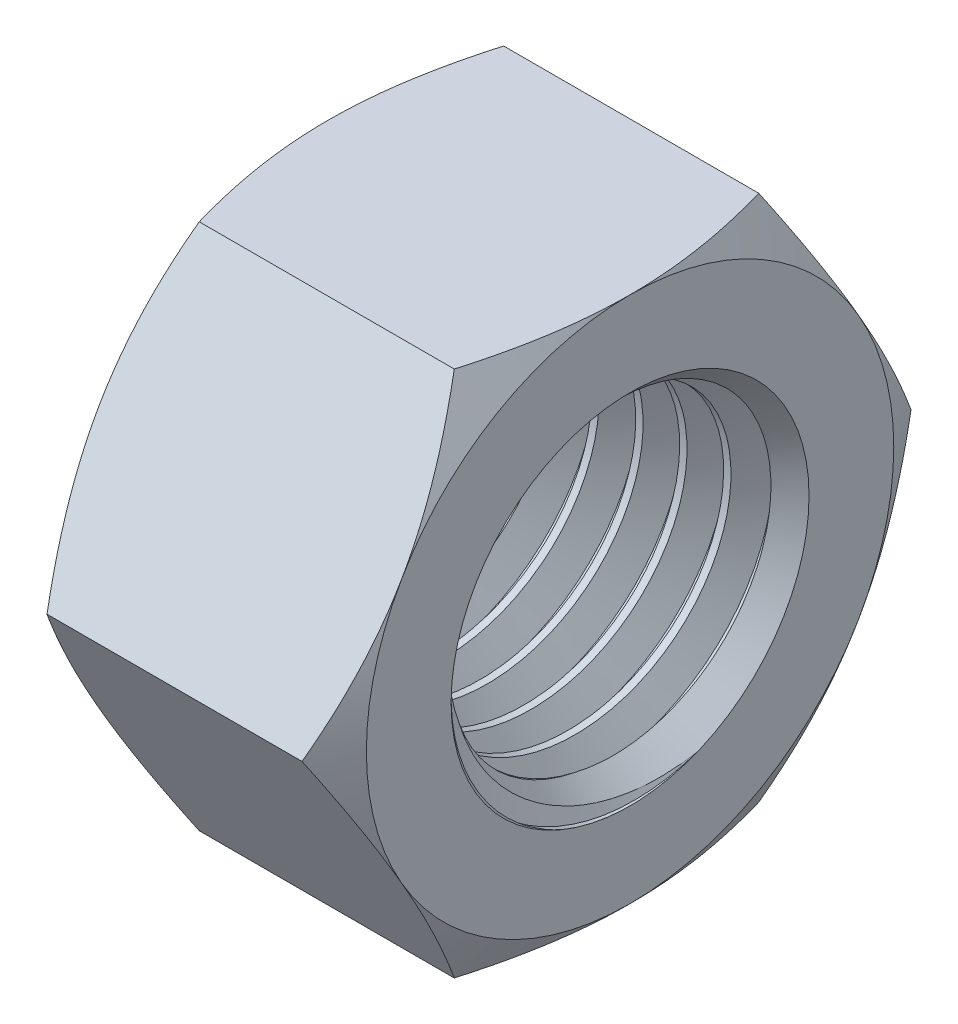
SolidWorks part; units mm, degrees
ref_plane "Front Plane" through (0, 0, 0) normal (0, 0, 1) x (1, 0, 0)
ref_plane "Top Plane" through (0, 0, 0) normal (0, 1, 0) x (1, 0, 0)
ref_plane "Right Plane" through (0, 0, 0) normal (1, 0, 0) x (0, 0, -1)
sketch "Sketch1" plane through (0, 0, 0) normal (1, 0, 0) x (0, 0, -1)
  line L1 (21.997, 0) -> (10.9985, 19.05)
  line L2 (10.9985, 19.05) -> (-10.9985, 19.05)
  line L3 (-10.9985, 19.05) -> (-21.997, 0)
  line L4 (-21.997, 0) -> (-10.9985, -19.05)
  line L5 (-10.9985, -19.05) -> (10.9985, -19.05)
  line L6 (10.9985, -19.05) -> (21.997, 0)
  circle A0 centre (0, 0) radius 19.05 construction
  circle A1 centre (0, 0) radius 10.9817
  dimension "D2" = 21.9634
  dimension "D1" = 38.1
extrude "Boss-Extrude1" add sketch "Sketch1" along normal mid plane 21.8281
sketch "Sketch2" plane through (10.9141, 0, 0) normal (1, 0, 0) x (0, 0, -1)
  line L0 (21.997, 0) -> (10.9985, 19.05) construction
  circle A0 centre (0, 0) radius 19.05
sketch "Sketch3" plane through (0, 0, 0) normal (0, 1, 0) x (1, 0, 0)
  line L0 (10.9141, 19.05) -> (7.2479, 25.4)
  line L1 (10.9141, 21.997) -> (10.9141, 10.9985) construction
  line L2 (7.2479, 25.4) -> (10.9141, 25.4)
  line L3 (10.9141, 25.4) -> (10.9141, 19.05)
  line L6 (-12.4808, 0) -> (21.7087, 0) construction
  line L7 (-12.0055, 0) -> (12.0055, 0) construction
  dimension "D1" = 30
  dimension "D2" = 6.35
revolve "Cut-Revolve1" cut sketch "Sketch3" angle 360 about L6
mirror "Mirror1" about plane through (0, 0, 0) normal (1, 0, 0) of "Cut-Revolve1"
chamfer "Chamfer1" distance 1.9482 angle 45 2 edges at (-10.9141, 0, -10.9817) (10.9141, 0, -10.9817)
ref_plane "Plane1" through (14.0891, 0, 0) normal (1, 0, 0) x (0, 0, -1)
sketch "Sketch4" plane through (14.0891, 0, 0) normal (1, 0, 0) x (0, 0, -1)
  circle A0 centre (0, 0) radius 10.9817 construction
  circle A1 centre (0, 0) radius 10.9817
curve "Helix/Spiral1" pitch 3.175 height 31.75 radius 10.9817 centre (14.0891, 0, 0) axis (-1, 0, 0) start towards (0, 0, -1)
sketch "Sketch5" plane through (0, 0, 0) normal (0, 0, 1) x (1, 0, 0)
  line L0 (14.0891, -13.4075) -> (14.0891, 4.6562) construction
  line L1 (14.0891, -20.955) -> (14.0891, 20.955) construction
  line L2 (7.7438, -10.9812) -> (21.2497, -10.9812) construction
  line L3 (13.8906, -12.9294) -> (14.2876, -12.9294)
  line L4 (14.2876, -12.9294) -> (15.5129, -10.807)
  line L5 (13.8906, -12.9294) -> (12.6652, -10.807)
  line L6 (15.5129, -10.807) -> (12.6652, -10.807)
  spline S0 degree 3 poles (14.0891, -10.9817) (14.0233, -10.9817) (13.8904, -10.4099) (13.6922, -7.9674) (13.4937, -4.3119) (13.2953, 0) (13.0969, 4.3119) (12.8984, 7.9674) (12.7, 10.4099) (12.5016, 11.2676) (12.3031, 10.4099) (12.1047, 7.9674) (11.8401, 3.0934) (11.5755, -3.0934) (11.3109, -7.9674) (11.1125, -10.4099) (10.9141, -11.2676) (10.7156, -10.4099) (10.5172, -7.9674) (10.2526, -3.0934) (9.988, 3.0934) (9.7234, 7.9674) (9.525, 10.4099) (9.3266, 11.2676) (9.1281, 10.4099) (8.9297, 7.9674) (8.6651, 3.0934) (8.4005, -3.0934) (8.1359, -7.9674) (7.9375, -10.4099) (7.7391, -11.2676) (7.5406, -10.4099) (7.3422, -7.9674) (7.0776, -3.0934) (6.813, 3.0934) (6.5484, 7.9674) (6.35, 10.4099) (6.1516, 11.2676) (5.9531, 10.4099) (5.7547, 7.9674) (5.4901, 3.0934) (5.2255, -3.0934) (4.9609, -7.9674) (4.7625, -10.4099) (4.5641, -11.2676) (4.3656, -10.4099) (4.1672, -7.9674) (3.9026, -3.0934) (3.638, 3.0934) (3.3734, 7.9674) (3.175, 10.4099) (2.9766, 11.2676) (2.7781, 10.4099) (2.5797, 7.9674) (2.3151, 3.0934) (2.0505, -3.0934) (1.7859, -7.9674) (1.5875, -10.4099) (1.3891, -11.2676) (1.1906, -10.4099) (0.9922, -7.9674) (0.7276, -3.0934) (0.463, 3.0934) (0.1984, 7.9674) (0, 10.4099) (-0.1984, 11.2676) (-0.3969, 10.4099) (-0.5953, 7.9674) (-0.8599, 3.0934) (-1.1245, -3.0934) (-1.3891, -7.9674) (-1.5875, -10.4099) (-1.7859, -11.2676) (-1.9844, -10.4099) (-2.1828, -7.9674) (-2.4474, -3.0934) (-2.712, 3.0934) (-2.9766, 7.9674) (-3.175, 10.4099) (-3.3734, 11.2676) (-3.5719, 10.4099) (-3.7703, 7.9674) (-4.0349, 3.0934) (-4.2995, -3.0934) (-4.5641, -7.9674) (-4.7625, -10.4099) (-4.9609, -11.2676) (-5.1594, -10.4099) (-5.3578, -7.9674) (-5.6224, -3.0934) (-5.887, 3.0934) (-6.1516, 7.9674) (-6.35, 10.4099) (-6.5484, 11.2676) (-6.7469, 10.4099) (-6.9453, 7.9674) (-7.2099, 3.0934) (-7.4745, -3.0934) (-7.7391, -7.9674) (-7.9375, -10.4099) (-8.1359, -11.2676) (-8.3344, -10.4099) (-8.5328, -7.9674) (-8.7974, -3.0934) (-9.062, 3.0934) (-9.3266, 7.9674) (-9.525, 10.4099) (-9.7234, 11.2676) (-9.9219, 10.4099) (-10.1203, 7.9674) (-10.3849, 3.0934) (-10.6495, -3.0934) (-10.9141, -7.9674) (-11.1125, -10.4099) (-11.3109, -11.2676) (-11.5094, -10.4099) (-11.7078, -7.9674) (-11.9724, -3.0934) (-12.237, 3.0934) (-12.5016, 7.9674) (-12.7, 10.4099) (-12.8984, 11.2676) (-13.0969, 10.4099) (-13.2953, 7.9674) (-13.5599, 3.0934) (-13.8245, -3.0934) (-14.0891, -7.9674) (-14.2875, -10.4099) (-14.4859, -11.2676) (-14.6844, -10.4099) (-14.8828, -7.9674) (-15.1474, -3.0934) (-15.412, 3.0934) (-15.6766, 7.9674) (-15.875, 10.4099) (-16.0734, 11.2676) (-16.2719, 10.4099) (-16.4703, 7.9674) (-16.6687, 4.3119) (-16.8672, 0) (-17.0656, -4.3119) (-17.2641, -7.9674) (-17.4623, -10.4099) (-17.5952, -10.9817) (-17.6609, -10.9817) knots 0 0 0 0 0.00625 0.0125 0.01875 0.025 0.03125 0.0375 0.04375 0.05 0.05625 0.0625 0.06875 0.08125 0.0875 0.09375 0.1 0.10625 0.1125 0.11875 0.13125 0.1375 0.14375 0.15 0.15625 0.1625 0.16875 0.18125 0.1875 0.19375 0.2 0.20625 0.2125 0.21875 0.23125 0.2375 0.24375 0.25 0.25625 0.2625 0.26875 0.28125 0.2875 0.29375 0.3 0.30625 0.3125 0.31875 0.33125 0.3375 0.34375 0.35 0.35625 0.3625 0.36875 0.38125 0.3875 0.39375 0.4 0.40625 0.4125 0.41875 0.43125 0.4375 0.44375 0.45 0.45625 0.4625 0.46875 0.48125 0.4875 0.49375 0.5 0.50625 0.5125 0.51875 0.53125 0.5375 0.54375 0.55 0.55625 0.5625 0.56875 0.58125 0.5875 0.59375 0.6 0.60625 0.6125 0.61875 0.63125 0.6375 0.64375 0.65 0.65625 0.6625 0.66875 0.68125 0.6875 0.69375 0.7 0.70625 0.7125 0.71875 0.73125 0.7375 0.74375 0.75 0.75625 0.7625 0.76875 0.78125 0.7875 0.79375 0.8 0.80625 0.8125 0.81875 0.83125 0.8375 0.84375 0.85 0.85625 0.8625 0.86875 0.88125 0.8875 0.89375 0.9 0.90625 0.9125 0.91875 0.93125 0.9375 0.94375 0.95 0.95625 0.9625 0.96875 0.975 0.98125 0.9875 0.99375 1 1 1 1 construction
  point P11 (14.0891, -12.9294)
  point P13 (14.0891, -10.807)
  dimension "D1" = 0.397
  dimension "D2" = 60
  dimension "D3" = 1.9482
sweep "Cut-Sweep1" cut profiles "Sketch5" path "Helix/Spiral1" align with end faces yes
